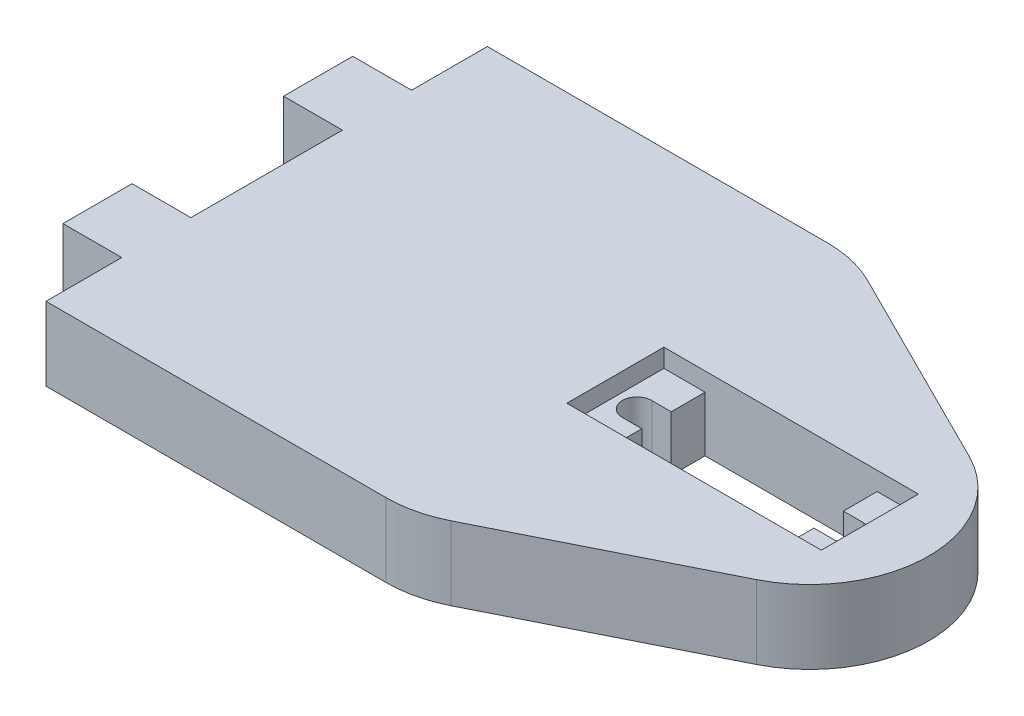
SolidWorks part; units mm, degrees
ref_plane "Front Plane" through (0, 0, 0) normal (0, 0, 1) x (1, 0, 0)
ref_plane "Top Plane" through (0, 0, 0) normal (0, 1, 0) x (1, 0, 0)
ref_plane "Right Plane" through (0, 0, 0) normal (1, 0, 0) x (0, 0, -1)
sketch "Sketch1" plane through (0, 0, 0) normal (0, 1, 0) x (1, 0, 0)
  line L0 (0, 0) -> (0, 10)
  line L13 (0, 10) -> (-8, 10)
  line L14 (-8, 10) -> (-8, 20)
  line L16 (-8, 20) -> (0, 20)
  line L17 (0, 20) -> (0, 40)
  line L18 (0, 40) -> (-8, 40)
  line L19 (-8, 40) -> (-8, 50)
  line L20 (-8, 50) -> (0, 50)
  line L21 (0, 50) -> (0, 60)
  line L22 (0, 60) -> (50, 60)
  line L23 (50, 60) -> (90, 40)
  line L24 (90, 40) -> (90, 20)
  line L25 (90, 20) -> (50, 0)
  line L26 (50, 0) -> (0, 0)
  dimension "D1" = 10
  dimension "D2" = 10
  dimension "D3" = 20
  dimension "D4" = 10
  dimension "D5" = 10
  dimension "D6" = 8
  dimension "D7" = 8
  dimension "D8" = 50
  dimension "D9" = 40
  dimension "D10" = 50
  dimension "D11" = 20
  dimension "D12" = 20
extrude "Boss-Extrude2" add sketch "Sketch1" along normal blind 10
sketch "Sketch5" plane through (0, 10, 0) normal (0, 1, 0) x (1, 0, 0)
  line L0 (90, 40) -> (50, 60) construction
  line L1 (50, 0) -> (90, 20) construction
  line L2 (90, 20) -> (90, 40) construction
  line L3 (81.0557, 44.4721) -> (90, 40)
  line L4 (90, 40) -> (90, 20)
  line L5 (90, 20) -> (81.0557, 15.5279)
  arc A0 (81.0557, 44.4721) -> (81.0557, 15.5279) centre (73.8197, 30) cw
  line M2 (50, 0) -> (90, 20)
  line M3 (90, 20) -> (90, 40)
  line M4 (90, 40) -> (50, 60)
extrude "Cut-Extrude2" cut sketch "Sketch5" against normal blind 10 contours A0 L4 M4 | A0 M3 M2 region at (88.1125, 10, -21.1665) region at (88.1125, 10, -38.8335)
fillet "Fillet3" radius 16 2 edges at (50, 5, -60) (50, 5, 0)
sketch "Sketch6" plane through (0, 10, 0) normal (0, 1, 0) x (1, 0, 0)
  line L1 (76.4, 36.6) -> (53, 36.6)
  line L2 (76.4, 36.6) -> (76.4, 23.4)
  line L3 (76.4, 23.4) -> (53, 23.4)
  line L4 (53, 36.6) -> (53, 23.4)
  arc A0 (81.0557, 15.5279) -> (81.0557, 44.4721) centre (73.8197, 30) ccw construction
  point P4 (76.4, 30)
  point P5 (90, 30)
  point P6 (70, 30)
  dimension "D1" = 23.4
  dimension "D2" = 13.2
  dimension "D3" = 13.6
  dimension "D4" = 6.4
extrude "Cut-Extrude3" cut sketch "Sketch6" against normal blind 10
sketch "Sketch7" plane through (0, 10, 0) normal (0, 1, 0) x (1, 0, 0)
  line L0 (64.7, 36.6) -> (64.7, 23.4) construction
  line L1 (76.4, 36.6) -> (53, 36.6) construction
  line L2 (53, 23.4) -> (76.4, 23.4) construction
  line L3 (76.4, 23.4) -> (76.4, 36.6) construction
  line L4 (79.05, 32) -> (76.4, 32)
  line L5 (79.05, 28) -> (76.4, 28)
  line L6 (76.4, 32) -> (76.4, 28)
  line L7 (53, 32) -> (53, 28)
  line L8 (50.35, 28) -> (53, 28)
  line L9 (50.35, 32) -> (53, 32)
  arc A0 (79.05, 28) -> (79.05, 32) centre (79.05, 30) ccw
  arc A1 (50.35, 28) -> (50.35, 32) centre (50.35, 30) cw
  dimension "D1" = 2.65
  dimension "D2" = 4
extrude "Cut-Extrude4" cut sketch "Sketch7" against normal blind 10
sketch "Sketch8" plane through (0, 10, 0) normal (0, 1, 0) x (1, 0, 0)
  line L0 (-8, 50) -> (-8, 40) construction
  line L1 (0, 50) -> (-8, 50)
  line L2 (0, 50) -> (0, 49.7)
  line L3 (0, 49.7) -> (-8, 49.7)
  line L4 (-8, 50) -> (-8, 49.7)
  line L6 (0, 40) -> (-8, 40)
  line L7 (0, 40) -> (0, 40.3)
  line L8 (0, 40.3) -> (-8, 40.3)
  line L9 (-8, 40) -> (-8, 40.3)
  line L11 (-8, 20) -> (-8, 19.7)
  line L12 (0, 19.7) -> (-8, 19.7)
  line L13 (0, 20) -> (0, 19.7)
  line L14 (0, 20) -> (-8, 20)
  line L15 (-8, 10) -> (-8, 10.3)
  line L16 (0, 10.3) -> (-8, 10.3)
  line L17 (0, 10) -> (0, 10.3)
  line L18 (0, 10) -> (-8, 10)
  dimension "D1" = 0.3
  dimension "D2" = 0.3
extrude "Cut-Extrude5" cut sketch "Sketch8" against normal blind 10
sketch "Sketch10" plane through (0, 10, 0) normal (0, 1, 0) x (1, 0, 0)
  line L0 (76.4, 36.6) -> (53, 36.6) construction
  line L1 (82, 36.6) -> (47.4, 36.6)
  line L2 (82, 36.6) -> (82, 23.4)
  line L3 (82, 23.4) -> (47.4, 23.4)
  line L4 (47.4, 36.6) -> (47.4, 23.4)
  line L5 (53, 23.4) -> (76.4, 23.4) construction
  point P9 (0, 0)
  dimension "D1" = 5.6
  dimension "D2" = 5.6
extrude "Cut-Extrude6" cut sketch "Sketch10" against normal blind 2.5
